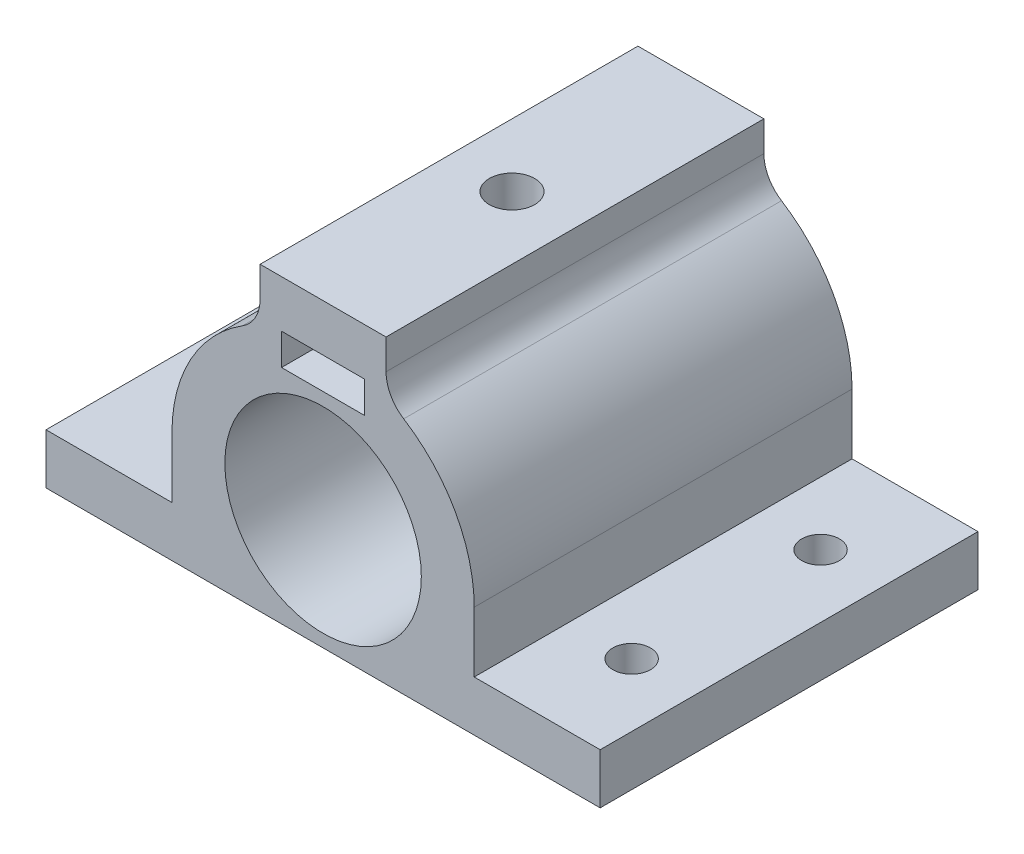
SolidWorks part; units mm, degrees
ref_plane "Plano frontal" through (0, 0, 0) normal (0, 0, 1) x (1, 0, 0)
ref_plane "Plano superior" through (0, 0, 0) normal (0, 1, 0) x (1, 0, 0)
ref_plane "Plano direito" through (0, 0, 0) normal (1, 0, 0) x (0, 0, -1)
sketch "Esboço1" plane through (0, 0, 0) normal (0, 0, 1) x (1, 0, 0)
  line L0 (-12, 0) -> (-12, -4.8)
  line L1 (22, -8.8) -> (-22, -8.8)
  line L2 (-22, -8.8) -> (-22, -4.8)
  line L3 (-22, -4.8) -> (-12, -4.8)
  line L4 (0, 11.0808) -> (0, -7.8) construction
  line L5 (22, -4.8) -> (12, -4.8)
  line L6 (22, -8.8) -> (22, -4.8)
  line L7 (12, 0) -> (12, -4.8)
  line L8 (0, 8.6919) -> (0, 15.0808) construction
  line L9 (5, 12.6886) -> (5, 15.0808)
  line L10 (-5, 12.6886) -> (-5, 15.0808)
  line L11 (-5, 8.6919) -> (-5, 15.0808) construction
  line L12 (5, 8.6919) -> (5, 15.0808) construction
  line L13 (5, 15.0808) -> (-5, 15.0808)
  line L14 (3.3, 11.3308) -> (-3.3, 11.3308)
  line L15 (3.3, 11.3308) -> (3.3, 8.8308)
  line L16 (3.3, 8.8308) -> (-3.3, 8.8308)
  line L17 (-3.3, 11.3308) -> (-3.3, 8.8308)
  line L18 (3.3, 11.3308) -> (-3.3, 8.8308) construction
  line L19 (3.3, 8.8308) -> (-3.3, 11.3308) construction
  arc A0 (7.8, 0) -> (-7.8, 0) centre (0, 0) ccw
  arc A1 (12, 0) -> (6.4, 10.1509) centre (0, 0) ccw
  arc A2 (-7.8, 0) -> (7.8, 0) centre (0, 0) ccw
  arc A3 (-6.4, 10.1509) -> (-12, 0) centre (0, 0) ccw
  arc A4 (-6.4, 10.1509) -> (-5, 12.6886) centre (-8, 12.6886) ccw
  arc A5 (6.4, 10.1509) -> (5, 12.6886) centre (8, 12.6886) cw
  point P15 (0, -8.8)
  point P22 (0, 10.0808)
  dimension "D1" = 7.8
  dimension "D2" = 12
  dimension "D3" = 7.8
  dimension "D9" = 3
  dimension "D4" = 5
  dimension "D5" = 10
  dimension "D6" = 5
  dimension "D7" = 4
  dimension "D8" = 5
extrude "Ressalto-extrusão1" add sketch "Esboço1" along normal blind 30
sketch "Esboço2" plane through (0, -4.8, 0) normal (0, 1, 0) x (1, 0, 0)
  line L0 (-12, -15) -> (-22, -15) construction
  line L1 (-12, -30) -> (-12, 0) construction
  line L2 (-22, -30) -> (-22, 0) construction
  line L3 (-17, -22.5) -> (-17, -7.5) construction
  line L4 (0, 0) -> (0, -28.0681) construction
  line L5 (17, -22.5) -> (17, -7.5) construction
  line L6 (12, -15) -> (22, -15) construction
  circle A0 centre (-17, -7.5) radius 1.5
  circle A1 centre (-17, -22.5) radius 1.5
  circle A2 centre (17, -22.5) radius 1.5
  circle A3 centre (17, -7.5) radius 1.5
  point P9 (-17, -15)
  point P20 (17, -15)
  dimension "D1" = 3
  dimension "D2" = 15
extrude "Corte-extrusão1" cut sketch "Esboço2" against normal blind 26
sketch "Esboço4" plane through (0, 15.0808, 0) normal (0, 1, 0) x (1, 0, 0)
  line L0 (0, -30) -> (0, 0) construction
  line L1 (5, -30) -> (-5, -30) construction
  line L2 (5, 0) -> (-5, 0) construction
  circle A0 centre (0, -15) radius 1.8
extrude "Corte-extrusão2" cut sketch "Esboço4" against normal blind 16
